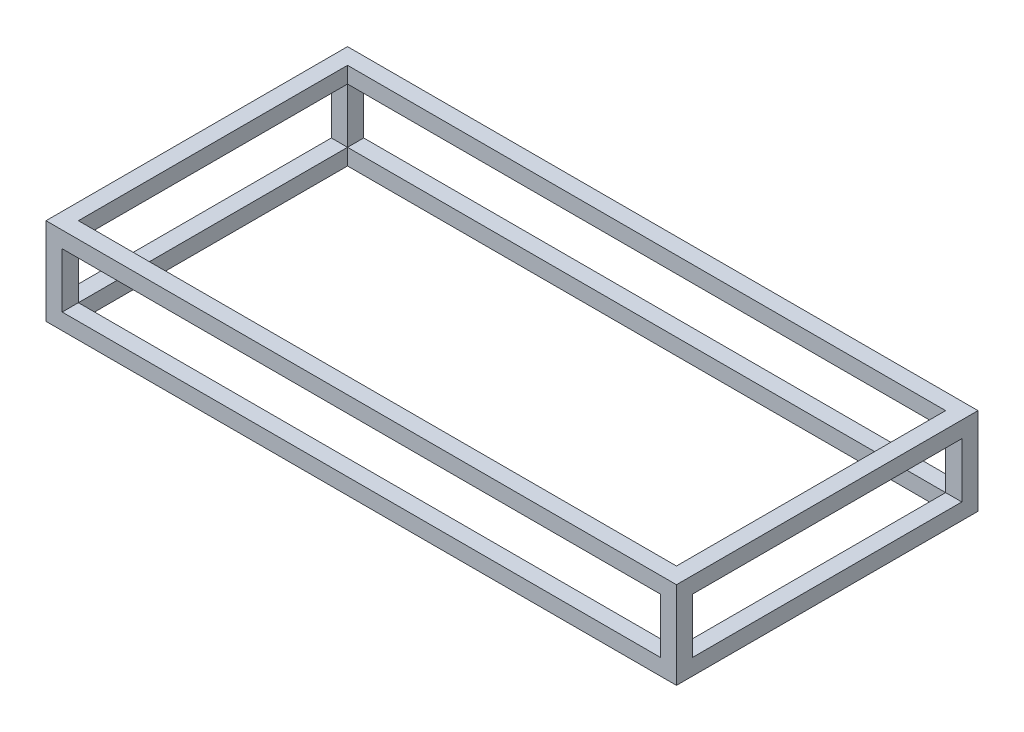
SolidWorks part; units mm, degrees
ref_plane "Front Plane" through (0, 0, 0) normal (0, 0, 1) x (1, 0, 0)
ref_plane "Top Plane" through (0, 0, 0) normal (0, 1, 0) x (1, 0, 0)
ref_plane "Right Plane" through (0, 0, 0) normal (1, 0, 0) x (0, 0, -1)
sketch "Sketch3" plane through (0, 0, 0) normal (0, 1, 0) x (1, 0, 0)
  line L1 (-277.1, 124.7) -> (277.1, 124.7)
  line L2 (-277.1, 124.7) -> (-277.1, -124.7)
  line L3 (-277.1, -124.7) -> (277.1, -124.7)
  line L4 (277.1, 124.7) -> (277.1, -124.7)
  line L5 (-277.1, 124.7) -> (277.1, -124.7) construction
  line L6 (-277.1, -124.7) -> (277.1, 124.7) construction
  line L7 (-292.1, 139.7) -> (292.1, 139.7)
  line L8 (-292.1, 139.7) -> (-292.1, -139.7)
  line L9 (-292.1, -139.7) -> (292.1, -139.7)
  line L10 (292.1, 139.7) -> (292.1, -139.7)
  line L11 (-292.1, 139.7) -> (292.1, -139.7) construction
  line L12 (-292.1, -139.7) -> (292.1, 139.7) construction
  point P0 (0, 0)
  point P6 (0, 0)
  dimension "D1" = 584.2
  dimension "D2" = 15
  dimension "D3" = 15
  dimension "D4" = 279.4
extrude "Boss-Extrude3" add sketch "Sketch3" along normal blind 15
sketch "Sketch4" plane through (0, 15, 0) normal (0, 1, 0) x (1, 0, 0)
  line L0 (-277.1, -124.7) -> (277.1, -124.7) construction
  line L1 (-292.1, 139.7) -> (-277.1, 139.7)
  line L2 (-292.1, 139.7) -> (-292.1, 124.7)
  line L3 (-292.1, 124.7) -> (-277.1, 124.7)
  line L4 (-277.1, 139.7) -> (-277.1, 124.7)
  line L5 (-292.1, -139.7) -> (-277.1, -139.7)
  line L6 (-292.1, -139.7) -> (-292.1, -124.7)
  line L7 (-292.1, -124.7) -> (-277.1, -124.7)
  line L8 (-277.1, -139.7) -> (-277.1, -124.7)
  line L9 (292.1, -139.7) -> (277.1, -139.7)
  line L10 (292.1, -139.7) -> (292.1, -124.7)
  line L11 (292.1, -124.7) -> (277.1, -124.7)
  line L12 (277.1, -139.7) -> (277.1, -124.7)
  line L14 (292.1, 139.7) -> (277.1, 139.7)
  line L15 (292.1, 139.7) -> (292.1, 124.7)
  line L16 (292.1, 124.7) -> (277.1, 124.7)
  line L17 (277.1, 139.7) -> (277.1, 124.7)
extrude "Boss-Extrude4" add sketch "Sketch4" along normal blind 50.8
sketch "Sketch5" plane through (0, 65.8, 0) normal (0, 1, 0) x (1, 0, 0)
  line L1 (-292.1, 139.7) -> (292.1, 139.7)
  line L2 (-292.1, 139.7) -> (-292.1, -139.7)
  line L3 (-292.1, -139.7) -> (292.1, -139.7)
  line L4 (292.1, 139.7) -> (292.1, -139.7)
  line L5 (-277.1, 124.7) -> (277.1, 124.7)
  line L6 (-277.1, 124.7) -> (-277.1, -124.7)
  line L7 (-277.1, -124.7) -> (277.1, -124.7)
  line L8 (277.1, 124.7) -> (277.1, -124.7)
extrude "Boss-Extrude6" add sketch "Sketch5" along normal blind 15
